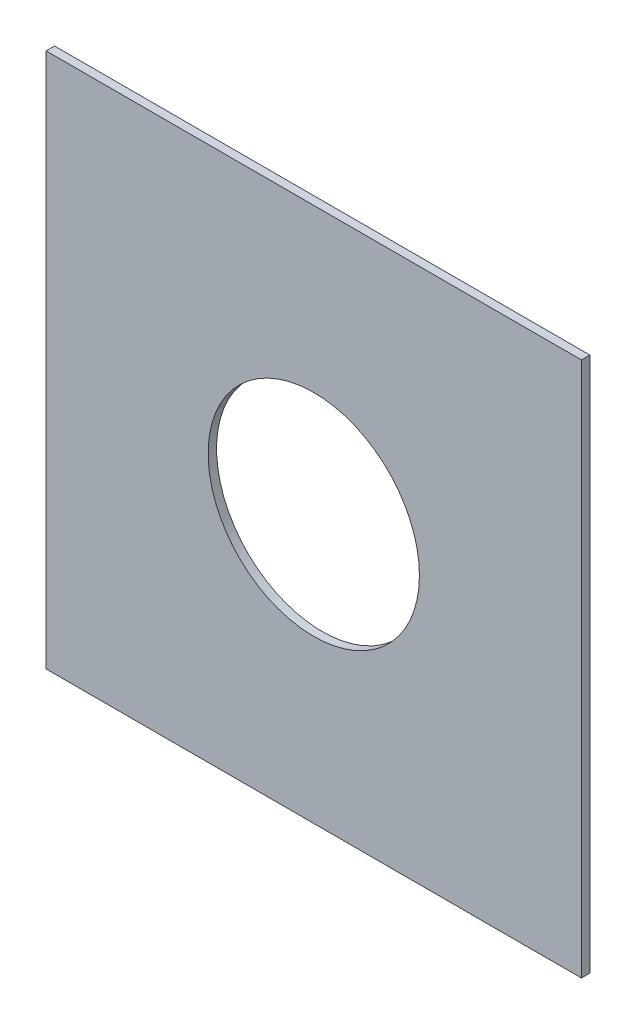
SolidWorks part; units mm, degrees
note: The reader was unsure of these and kept them because the rebuilt part matched: thickness of "Main Plate", "Sheet-Metal1".
material "Acrylic (Medium-high impact)"
ref_plane "Front Plane" through (0, 0, 0) normal (0, 0, 1) x (1, 0, 0)
ref_plane "Top Plane" through (0, 0, 0) normal (0, 1, 0) x (1, 0, 0)
ref_plane "Right Plane" through (0, 0, 0) normal (1, 0, 0) x (0, 0, -1)
sketch "Sketch1" plane through (0, 0, 0) normal (0, 0, 1) x (1, 0, 0)
  line L1 (-95, -95) -> (95, -95)
  line L2 (-95, -95) -> (-95, 95)
  line L3 (-95, 95) -> (95, 95)
  line L4 (95, -95) -> (95, 95)
  line L5 (-95, -95) -> (95, 95) construction
  line L6 (-95, 95) -> (95, -95) construction
  circle A2 centre (0, 0) radius 37.5
  circle A3 centre (0, 0) radius 37.5
  point P0 (0, 0)
  dimension "D2" = 5
  dimension "D3" = 75
  dimension "D1" = 190
base flange "Main Plate" sketch "Sketch1" thickness 3 reverse thickness direction no parameters "D1"=4.5
sketch "Bend-Lines1" [suppressed] plane through (0, 0, 0) normal (0, 1, 0) x (1, 0, 0)
sketch "Bounding-Box1" [suppressed]
sheet metal parameters "Sheet-Metal1" thickness 3 parameters "D1"=1.5, "D7"=5
flat pattern "Flat-Pattern1" [suppressed]
sketch "Bend-Lines2" plane through (0, 0, 0) normal (0, 1, 0) x (1, 0, 0)
sketch3d "Bounding-Box2" [suppressed]
  line L0 (-95, -95, 0) -> (95, -95, 0) construction
  line L1 (-95, 95, 0) -> (95, 95, 0) construction
  line L2 (-95, -95, 0) -> (-95, 95, 0) construction
  line L3 (95, -95, 0) -> (95, 95, 0) construction
